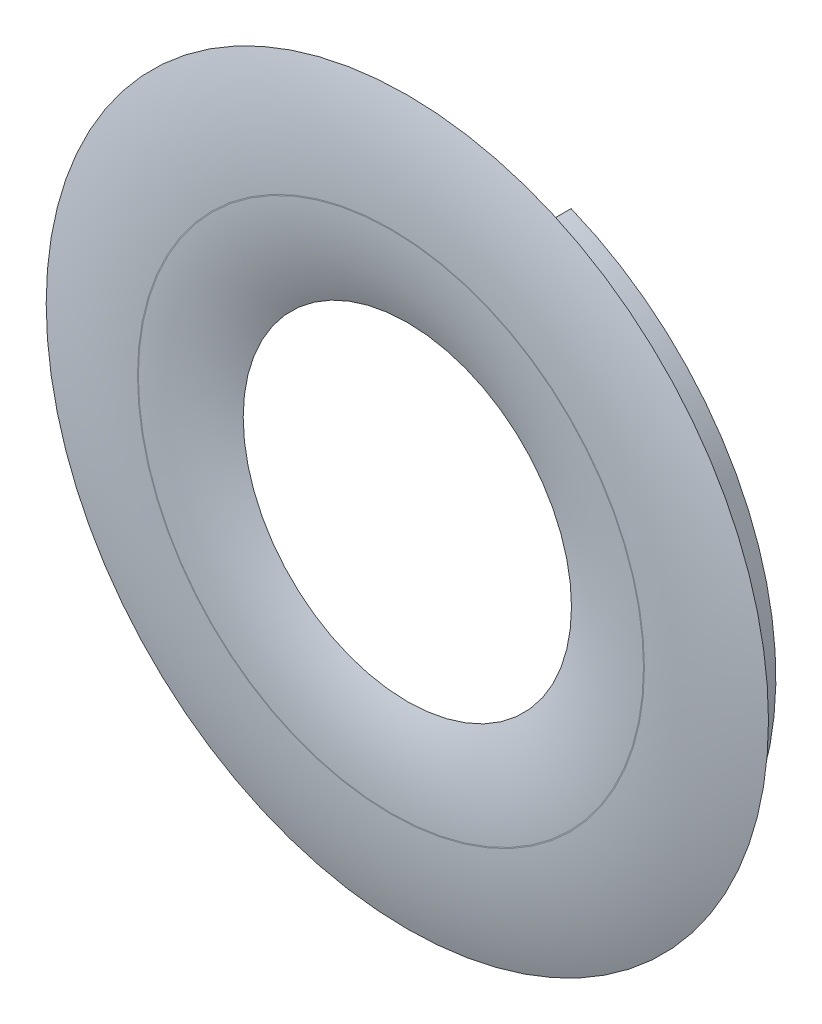
SolidWorks part; units mm, degrees
ref_plane "Front Plane" through (0, 0, 0) normal (0, 0, 1) x (1, 0, 0)
ref_plane "Top Plane" through (0, 0, 0) normal (0, 1, 0) x (1, 0, 0)
ref_plane "Right Plane" through (0, 0, 0) normal (1, 0, 0) x (0, 0, -1)
sketch "Sketch2" plane through (0, 0, 0) normal (0, 0, 1) x (1, 0, 0)
  line L0 (0, 21.2988) -> (0, -21.2414) construction
  line L1 (21.2512, 0) -> (-20.98, 0) construction
  line L2 (-6.771, 21.2988) -> (-6.771, 13.4975) construction
  line L3 (7.619, 21.2988) -> (7.619, 13.4975) construction
  line L4 (-5.576, 21.2988) -> (-5.576, 13.4975) construction
  line L5 (6.424, 21.2988) -> (6.424, 13.4975) construction
  line L6 (-12.776, 4.168) -> (-22.3004, 4.168) construction
  line L7 (-12.776, -4.472) -> (-22.0416, -4.472) construction
  line L8 (0, 0) -> (15.7682, 15.3415) construction
  line L9 (0, 0) -> (-15.9956, -16.2813) construction
  circle A0 centre (0, 0) radius 19.627 construction
  circle A1 centre (-9.976, 10.023) radius 0.9 construction
  circle A2 centre (10.199, 9.923) radius 1.2 construction
  circle A3 centre (-9.851, -10.027) radius 1.2 construction
  dimension "D4" = 39.254
  dimension "D1" = 14.39
  dimension "D2" = 1.195
  dimension "D3" = 12
  dimension "D5" = 44.8213
  dimension "D6" = 42.5403
  dimension "D7" = 30.0874
  dimension "D8" = 29.8556
  dimension "D9" = 8.64
  dimension "D10" = 4.168
  dimension "D11" = 9.923
  dimension "D12" = 10.199
  dimension "D13" = 10.027
  dimension "D14" = 9.851
  dimension "D15" = 20.05
  dimension "D16" = 9.976
  dimension "D17" = 6.424
  dimension "D18" = 5.9573
  dimension "D19" = 30.0468
  dimension "D20" = 9.5244
  dimension "D21" = 9.2656
  dimension "D22" = 6.278
  dimension "D23" = 12.776
  dimension "D24" = 13.4975
  dimension "D25" = 13.4975
  dimension "D26" = 13.4975
  dimension "D27" = 13.4975
  dimension "D28" = 7.8013
  dimension "D29" = 7.8013
  dimension "D30" = 7.8013
  dimension "D31" = 7.8013
sketch "Sketch3" plane through (0, 0, 0) normal (0, 0, 1) x (1, 0, 0)
  circle A0 centre (0, 0) radius 22
  dimension "D1" = 44
extrude "Boss-Extrude1" add sketch "Sketch3" along normal blind 1
sketch "Sketch4" plane through (0, 0, 1) normal (0, 0, 1) x (1, 0, 0)
  circle A0 centre (0, 0) radius 20.25
  dimension "D1" = 40.5
sketch "Sketch6" plane through (0, 0, 0) normal (0, 0, -1) x (-1, 0, 0)
  circle A0 centre (0, 0) radius 19.5
  dimension "D1" = 39
sketch "Sketch7" plane through (0, 0, 1) normal (0, 0, 1) x (1, 0, 0)
  circle A0 centre (0, 0) radius 10
  dimension "D1" = 20
extrude "Cut-Extrude1" cut sketch "Sketch7" against normal blind 10
fillet "Fillet7" radius 22 1 edges at (22, 0, 1)
fillet "Fillet8" radius 15 1 edges at (10, 0, 1)
sketch "Sketch8" plane through (0, 0, 0) normal (0, 0, -1) x (-1, 0, 0)
  circle A0 centre (0, 0) radius 19.95
  dimension "D1" = 39.9
extrude "Boss-Extrude2" add sketch "Sketch8" along normal blind 2.5 contours A0
sketch "Sketch9" plane through (0, 0, -2.5) normal (0, 0, -1) x (-1, 0, 0)
  circle A0 centre (0, 0) radius 19.2
  dimension "D1" = 38.4
extrude "Cut-Extrude2" cut sketch "Sketch9" against normal up to surface (2.5 mm away) up to face at (19.95, 0, 0)
sketch "Sketch10" plane through (0, 0, 0) normal (0, 0, -1) x (-1, 0, 0)
  line L1 (7.5234, 20.2964) -> (-7.4766, 20.2964)
  line L2 (7.5234, 20.2964) -> (7.5234, 17.2964)
  line L3 (7.5234, 17.2964) -> (-7.4766, 17.2964)
  line L4 (-7.4766, 20.2964) -> (-7.4766, 17.2964)
  dimension "D1" = 15
  dimension "D2" = 3
extrude "Cut-Extrude3" cut sketch "Sketch10" along normal blind 3
fillet "Fillet9" radius 1 1 edges at (0.0254, -19.2, 0)
